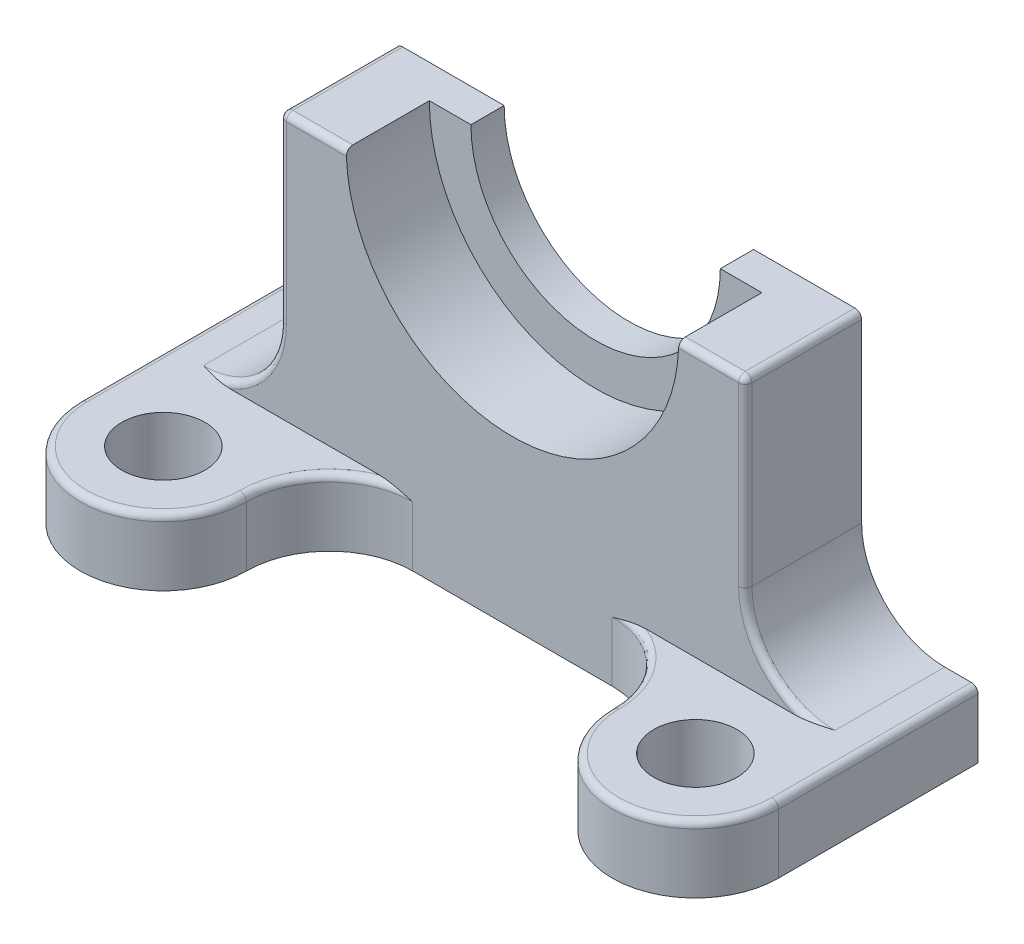
SolidWorks part; units mm, degrees
ref_plane "Front Plane" through (0, 0, 0) normal (0, 0, 1) x (1, 0, 0)
ref_plane "Top Plane" through (0, 0, 0) normal (0, 1, 0) x (1, 0, 0)
ref_plane "Right Plane" through (0, 0, 0) normal (1, 0, 0) x (0, 0, -1)
sketch "Sketch3" plane through (0, 0, 0) normal (0, 1, 0) x (1, 0, 0)
  line L0 (-141.5089, 53.4986) -> (125.1911, 53.4986)
  line L1 (125.1911, 53.4986) -> (125.1911, -22.7014)
  line L4 (29.9411, 9.0486) -> (-46.2589, 9.0486)
  line L7 (-141.5089, -22.7014) -> (-141.5089, 53.4986)
  arc A0 (61.6911, -22.7014) -> (29.9411, 9.0486) centre (29.9411, -22.7014) ccw
  arc A1 (-46.2589, 9.0486) -> (-78.0089, -22.7014) centre (-46.2589, -22.7014) ccw
  arc A2 (-141.5089, -22.7014) -> (-78.0089, -22.7014) centre (-109.7589, -22.7014) ccw
  arc A3 (61.6911, -22.7014) -> (125.1911, -22.7014) centre (93.4411, -22.7014) ccw
  circle A4 centre (93.4411, -22.7014) radius 15.875
  circle A5 centre (-109.7589, -22.7014) radius 15.875
  point P12 (-78.0089, 9.0486)
  point P19 (0, 0)
  point P21 (-38.0302, -42.197)
  dimension "D5" = 31.75
  dimension "D6" = 31.75
  dimension "D7" = 203.2
  dimension "D8" = 63.5
  dimension "D1" = 31.75
  dimension "D3" = 266.7
extrude "Boss-Extrude1" add sketch "Sketch3" against normal blind 25.4
sketch "Sketch4" plane through (0, 0, 0) normal (0, 1, 0) x (1, 0, 0)
  line L0 (125.1911, 53.4986) -> (-141.5089, 53.4986) construction
  line L1 (-97.0589, 53.4986) -> (80.7411, 53.4986)
  line L2 (-97.0589, 53.4986) -> (-97.0589, 9.0486)
  line L3 (-97.0589, 9.0486) -> (80.7411, 9.0486)
  line L4 (80.7411, 53.4986) -> (80.7411, 9.0486)
  line L5 (125.1911, -22.7014) -> (125.1911, 53.4986) construction
  dimension "D1" = 44.45
  dimension "D2" = 177.8
  dimension "D3" = 44.45
extrude "Boss-Extrude2" add sketch "Sketch4" along normal blind 101.6
fillet "Fillet3" radius 31.75 1 edges at (80.7411, 0, -31.2736) type face fillet first side face at (80.7411, 50.8, -31.2736) second side face at (85.012, 0, -9.0862)
fillet "Fillet4" radius 31.75 1 edges at (-97.0589, 0, -31.2736) type face fillet first side face at (-97.0589, 50.8, -31.2736) second side face at (-101.3298, 0, -9.0862)
sketch "Sketch5" plane through (0, 0, -9.0486) normal (0, 0, 1) x (1, 0, 0)
  line L0 (-8.1589, 101.6) -> (-8.1589, -25.4) construction
  line L1 (-97.0589, 101.6) -> (80.7411, 101.6) construction
  line L2 (-46.2589, -25.4) -> (29.9411, -25.4) construction
  circle A0 centre (-8.1589, 101.6) radius 63.5
  circle A1 centre (-8.1589, 101.6) radius 47.625
  dimension "D1" = 127
  dimension "D2" = 95.25
extrude "Cut-Extrude1" cut sketch "Sketch5" against normal through all contours A1
extrude "Cut-Extrude2" cut sketch "Sketch5<3>" against normal blind 31.75
sketch "Sketch5<3>" plane through (0, 0, -9.0486) normal (0, 0, 1) x (1, 0, 0) same geometry as "Sketch5"
fillet "Fillet5" radius 2.54 14 edges at (-68.7095, 0, 0.2508) (-109.7589, 0, 54.4514) (-141.5089, 0, -15.3986) (-97.0589, 101.6, -31.2736) (-97.0589, 66.675, -9.0486) (-106.3583, 9.2994, -9.0486) (80.7411, 101.6, -31.2736) (68.0411, 101.6, -9.0486) (80.7411, 66.675, -9.0486) (90.0405, 9.2994, -9.0486) (125.1911, 0, -15.3986) (93.4411, 0, 54.4514) (52.3917, 0, 0.2508) (-84.3589, 101.6, -9.0486)
